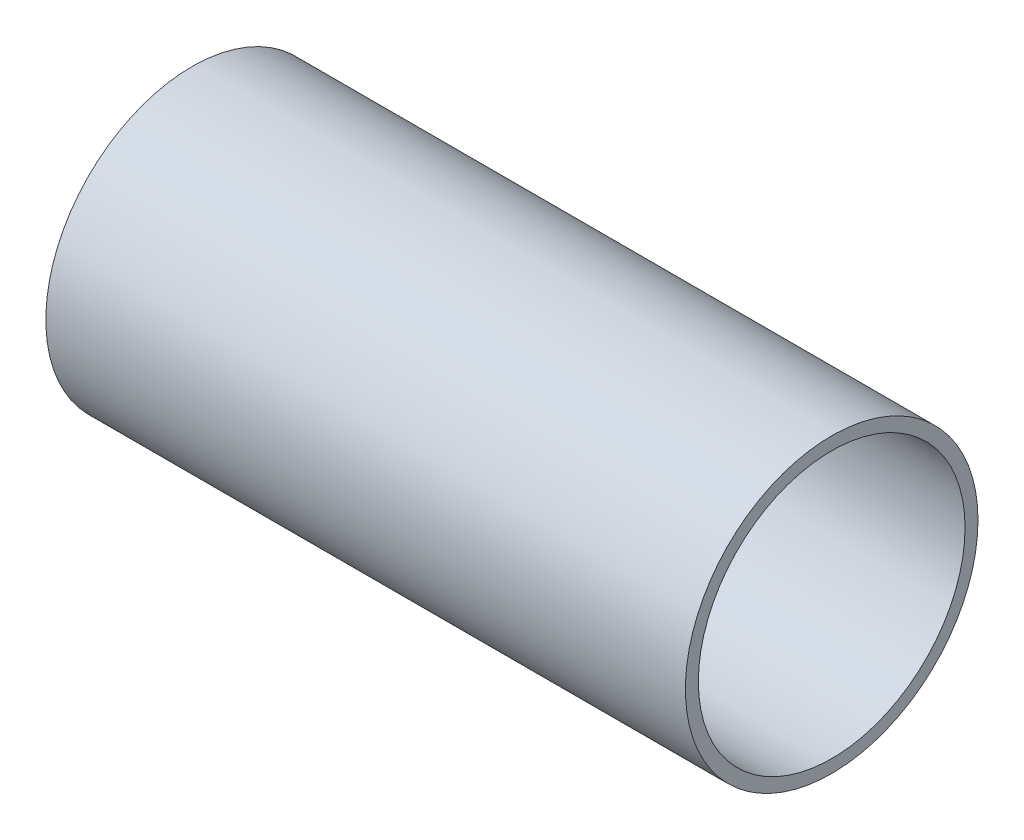
SolidWorks part; units mm, degrees
ref_plane "Vorne" through (0, 0, 0) normal (0, 0, 1) x (1, 0, 0)
ref_plane "Oben" through (0, 0, 0) normal (0, 1, 0) x (1, 0, 0)
ref_plane "Seite" through (0, 0, 0) normal (1, 0, 0) x (0, 0, -1)
sketch "Skizze1" plane through (0, 0, 0) normal (1, 0, 0) x (0, 0, -1)
  circle A0 centre (0, 0) radius 5.15
  circle A1 centre (0, 0) radius 5.65
  dimension "D1" = 10.3
  dimension "D2" = 11.3
extrude "Aufsatz-Linear austragen1" add sketch "Skizze1" along normal blind 24.7
